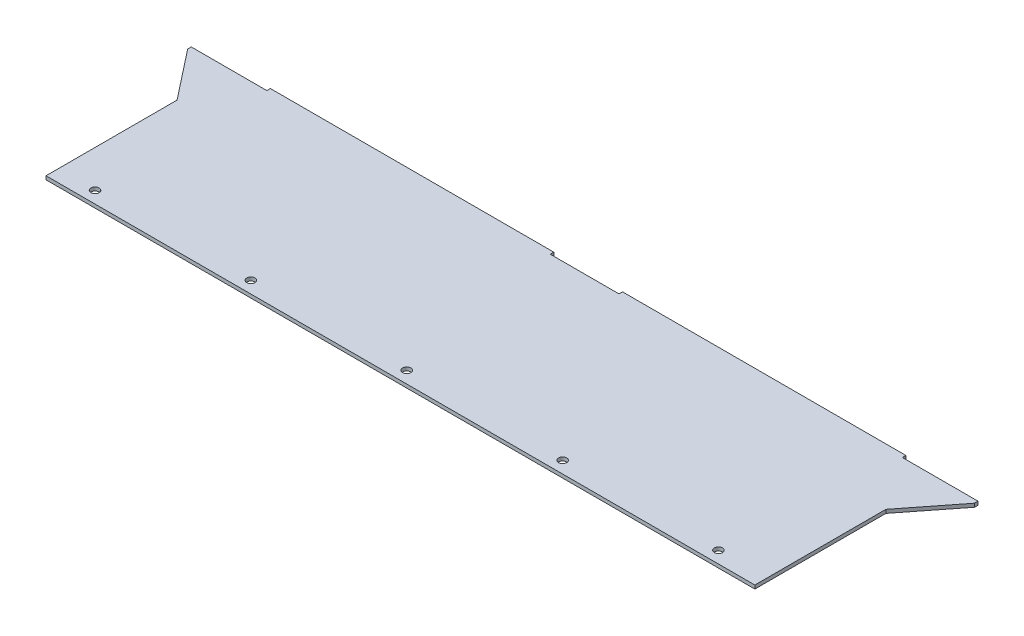
SolidWorks part; units mm, degrees
material "6061-T6 (SS)"
ref_plane "X-Y Datum" through (0, 0, 0) normal (0, 0, 1) x (1, 0, 0)
ref_plane "X-Z Datum" through (0, 0, 0) normal (0, 1, 0) x (1, 0, 0)
ref_plane "Y-Z Datum" through (0, 0, 0) normal (1, 0, 0) x (0, 0, -1)
sketch "Sketch1" plane through (0, 0, 0) normal (0, 1, 0) x (1, 0, 0)
  line L1 (-317.6778, 82.55) -> (317.6778, 82.55)
  line L2 (-317.6778, 82.55) -> (-317.6778, -82.55)
  line L3 (-317.6778, -82.55) -> (317.6778, -82.55)
  line L4 (317.6778, 82.55) -> (317.6778, -82.55)
  line L5 (-317.6778, 82.55) -> (317.6778, -82.55) construction
  line L6 (-317.6778, -82.55) -> (317.6778, 82.55) construction
  point P0 (0, 0)
  dimension "D1" = 635.3556
  dimension "D2" = 165.1
extrude "Boss-Extrude1" add sketch "Sketch1" along normal mid plane 3.175
sketch "Sketch2" plane through (0, 0, -82.55) normal (0, 0, -1) x (-1, 0, 0)
  line L20 (-317.6778, -1.5875) -> (317.6778, -1.5875) construction
  line L21 (-284.8229, -1.5875) -> (-30.8229, -1.5875)
  line L22 (30.8229, -1.5875) -> (284.8229, -1.5875)
  line L40 (30.8229, -1.5875) -> (30.8229, 1.5875)
  line L41 (30.8229, 1.5875) -> (284.8229, 1.5875)
  line L42 (284.8229, 1.5875) -> (284.8229, -1.5875)
  line L56 (-284.8229, -1.5875) -> (-284.8229, 1.5875)
  line L57 (-284.8229, 1.5875) -> (-30.8229, 1.5875)
  line L58 (-30.8229, 1.5875) -> (-30.8229, -1.5875)
extrude "Boss-Extrude2" add sketch "Sketch2" along normal blind 3.175
sketch "Sketch3" plane through (0, -1.5875, 0) normal (0, -1, 0) x (1, 0, 0)
  line L0 (317.6778, -82.55) -> (352.6028, -82.55)
  line L1 (352.6028, -82.55) -> (352.6028, -79.375)
  line L3 (352.6028, -79.375) -> (317.6778, -34.925)
  line L4 (317.6778, 82.55) -> (317.6778, -82.55) construction
  line L17 (317.6778, -82.55) -> (317.6778, 82.55)
  line L18 (317.6778, 82.55) -> (-317.6778, 82.55)
  line L19 (-317.6778, 82.55) -> (-317.6778, -82.55)
  line L20 (-317.6778, -82.55) -> (-284.8229, -82.55)
  line L21 (-284.8229, -82.55) -> (-284.8229, -85.725)
  line L22 (-284.8229, -85.725) -> (-30.8229, -85.725)
  line L23 (-30.8229, -85.725) -> (-30.8229, -82.55)
  line L24 (-30.8229, -82.55) -> (30.8229, -82.55)
  line L25 (30.8229, -82.55) -> (30.8229, -85.725)
  line L26 (30.8229, -85.725) -> (284.8229, -85.725)
  line L27 (284.8229, -85.725) -> (284.8229, -82.55)
  line L28 (284.8229, -82.55) -> (317.6778, -82.55)
  line L29 (317.6778, -82.55) -> (317.6778, -34.925)
  dimension "D1" = 34.925
  dimension "D2" = 3.175
  dimension "D3" = 44.45
  dimension "D4" = 0
extrude "Boss-Extrude3" add sketch "Sketch3" against normal blind 3.175
mirror "Mirror1" about plane through (0, 0, 0) normal (1, 0, 0) of "Boss-Extrude3"
sketch "Sketch4" plane through (0, -1.5875, 0) normal (0, -1, 0) x (1, 0, 0)
  line L0 (-284.4038, 82.55) -> (-284.4038, 71.882)
  line L1 (-317.6778, 82.55) -> (317.6778, 82.55) construction
  line L2 (-284.4038, 71.882) -> (-317.6778, 71.882)
  line L3 (-317.6778, -34.925) -> (-317.6778, 82.55) construction
  circle A0 centre (-284.4038, 71.882) radius 3.675
extrude "Cut-Extrude1" cut sketch "Sketch4" against normal through all contours L2 A0 L0 | L0 A0 L2 region at (-283.8839, -1.5875, 71.3621) region at (-285.9635, -1.5875, 73.4417)
pattern_linear "LPattern1" count 5 spacing 139.7 along (1, 0, 0) of "Cut-Extrude1"
